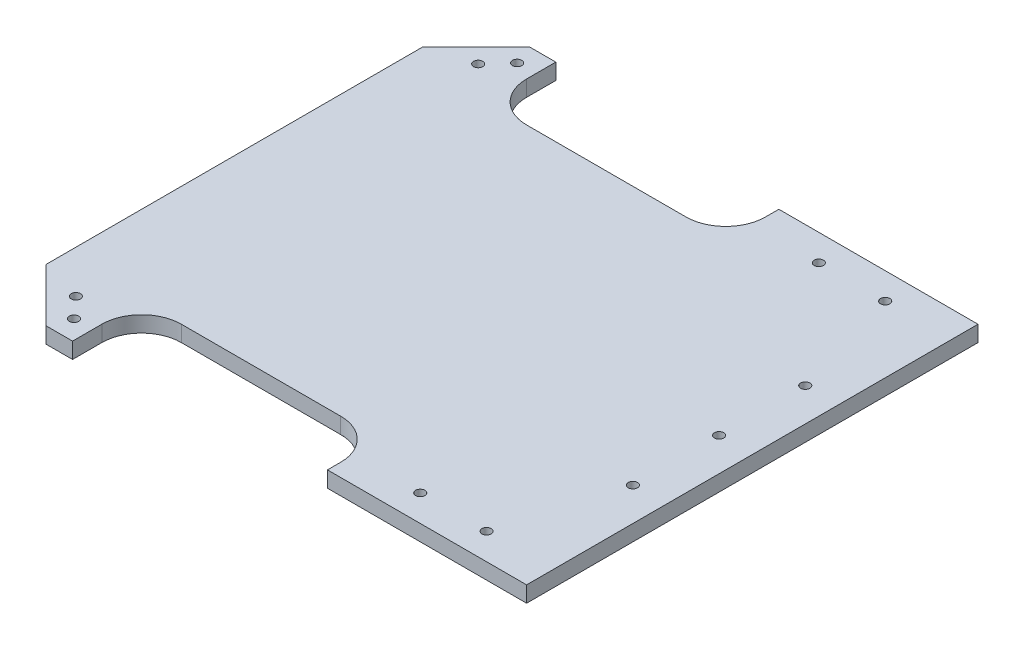
SolidWorks part; units mm, degrees
material "ABS"
ref_plane "Front Plane" through (0, 0, 0) normal (0, 0, 1) x (1, 0, 0)
ref_plane "Top Plane" through (0, 0, 0) normal (0, 1, 0) x (1, 0, 0)
ref_plane "Right Plane" through (0, 0, 0) normal (1, 0, 0) x (0, 0, -1)
sketch "Sketch1" plane through (0, 0, 0) normal (0, 1, 0) x (1, 0, 0)
  line L1 (-97.5, 85) -> (97.5, 85)
  line L2 (-97.5, 85) -> (-97.5, -85)
  line L3 (-97.5, -85) -> (97.5, -85)
  line L4 (97.5, 85) -> (97.5, -85)
  line L5 (-97.5, 85) -> (97.5, -85) construction
  line L6 (-97.5, -85) -> (97.5, 85) construction
  point P0 (0, 0)
  dimension "D1" = 195
  dimension "D2" = 170
extrude "Boss-Extrude1" add sketch "Sketch1" along normal blind 6
sketch "Sketch2" plane through (0, 6, 0) normal (0, 1, 0) x (1, 0, 0)
  line L0 (-97.5, -85) -> (-67.5, -85) construction
  line L1 (-97.5, -85) -> (97.5, -85) construction
  line L2 (0, 0) -> (-97.5, 0) construction
  line L3 (-67.5, -85) -> (22.5, -85)
  line L4 (-67.5, -85) -> (-67.5, -65)
  line L5 (-67.5, -65) -> (22.5, -65)
  line L6 (22.5, -85) -> (22.5, -65)
  line L7 (-97.5, 85) -> (-97.5, -85) construction
  line L8 (-67.5, 65) -> (22.5, 65)
  line L9 (22.5, 85) -> (22.5, 65)
  line L10 (-67.5, 85) -> (22.5, 85)
  line L11 (-67.5, 85) -> (-67.5, 65)
  dimension "D1" = 30
  dimension "D2" = 90
  dimension "D3" = 20
extrude "Cut-Extrude1" cut sketch "Sketch2" against normal through all
fillet "Fillet1" radius 15 4 edges at (22.5, 3, -65) (-67.5, 3, -65) (-67.5, 3, 65) (22.5, 3, 65)
sketch "Sketch3" plane through (0, 6, 0) normal (0, 1, 0) x (1, 0, 0)
  line L0 (0, 0) -> (-97.5, 0) construction
  line L1 (-67.5, 85) -> (-97.5, 85)
  line L2 (-67.5, 85) -> (-67.5, 91)
  line L3 (-67.5, 91) -> (-97.5, 91)
  line L4 (-97.5, 85) -> (-97.5, 91)
  line L5 (-97.5, 85) -> (-97.5, -85) construction
  line L6 (-67.5, -91) -> (-97.5, -91)
  line L7 (-97.5, -85) -> (-97.5, -91)
  line L8 (-67.5, -85) -> (-97.5, -85)
  line L9 (-67.5, -85) -> (-67.5, -91)
  dimension "D1" = 6
extrude "Boss-Extrude2" add sketch "Sketch3" against normal up to surface (6 mm away) up to face at (-16.875, 0, 0)
chamfer "Chamfer1" distance 20 angle 45 2 edges at (-97.5, 3, 91) (-97.5, 3, -91)
sketch "Sketch4" plane through (0, 6, 0) normal (0, 1, 0) x (1, 0, 0)
  line L0 (-67.5, 91) -> (-67.5, 80) construction
  line L1 (-67.5, 91.1) -> (-88.5, 91.1) construction
  line L2 (-67.5, 91.1) -> (-67.5, 68.1) construction
  line L3 (-67.5, 68.1) -> (-88.5, 68.1) construction
  line L4 (-88.5, 91.1) -> (-88.5, 68.1) construction
  line L7 (-88.5, 68.1) -> (-81.5, 75.7667) construction
  line L8 (-81.5, 75.7667) -> (-74.5, 83.4333) construction
  line L9 (-74.5, 83.4333) -> (-67.5, 91.1) construction
  line L10 (-97.5, 0) -> (0, 0) construction
  line L11 (-97.5, 71) -> (-97.5, -71) construction
  line L12 (-67.5, 91) -> (-77.5, 91) construction
  circle A0 centre (-81.5, 75.7667) radius 1.75
  circle A1 centre (-74.5, 83.4333) radius 1.75
  circle A2 centre (-74.5, -83.4333) radius 1.75
  circle A3 centre (-81.5, -75.7667) radius 1.75
  dimension "D4" = 3.5
  dimension "D5" = 3.5
  dimension "D1" = 23
  dimension "D2" = 21
  dimension "D3" = 0.1
extrude "Cut-Extrude2" cut sketch "Sketch4" against normal through all
sketch "Sketch7" plane through (0, 0, 0) normal (0, -1, 0) x (1, 0, 0)
  line L0 (97.5, 85) -> (97.5, -85) construction
  line L1 (22.5, 85.1) -> (97.5, 85.1) construction
  line L2 (22.5, 85.1) -> (22.5, 65) construction
  line L3 (22.5, 65) -> (97.5, 65) construction
  line L4 (97.5, 85.1) -> (97.5, 65) construction
  line L5 (22.5, 85) -> (22.5, 80) construction
  line L6 (22.5, 85) -> (97.5, 85) construction
  line L7 (22.5, 75.05) -> (47.5, 75.05) construction
  line L8 (47.5, 75.05) -> (72.5, 75.05) construction
  line L9 (72.5, 75.05) -> (97.5, 75.05) construction
  line L10 (0, 0) -> (97.5, 0) construction
  circle A0 centre (47.5, 75.05) radius 1.75
  circle A1 centre (72.5, 75.05) radius 1.75
  circle A2 centre (72.5, -75.05) radius 1.75
  circle A3 centre (47.5, -75.05) radius 1.75
  dimension "D3" = 3.5
  dimension "D4" = 3.5
  dimension "D1" = 0.1
  dimension "D2" = 20.1
extrude "Cut-Extrude5" cut sketch "Sketch7" against normal through all
sketch "Sketch8" plane through (0, 0, 0) normal (0, -1, 0) x (1, 0, 0)
  line L0 (97.5, 0) -> (72.5, 0) construction
  line L1 (97.5, 85) -> (97.5, -85) construction
  line L2 (85, 64.9) -> (85, 32.45) construction
  line L3 (72.5, 64.9) -> (97.5, 64.9) construction
  line L4 (72.5, 64.9) -> (72.5, -64.9) construction
  line L5 (72.5, -64.9) -> (97.5, -64.9) construction
  line L6 (97.5, 64.9) -> (97.5, -64.9) construction
  line L7 (72.5, 64.9) -> (97.5, -64.9) construction
  line L8 (72.5, -64.9) -> (97.5, 64.9) construction
  line L9 (85, 32.45) -> (85, 0) construction
  line L10 (85, 0) -> (85, -32.45) construction
  line L11 (85, -32.45) -> (85, -64.9) construction
  circle A0 centre (85, 32.45) radius 1.75
  circle A1 centre (85, 0) radius 1.75
  circle A2 centre (85, -32.45) radius 1.75
  point P5 (85, 0)
  dimension "D3" = 3.5
  dimension "D4" = 3.5
  dimension "D5" = 3.5
  dimension "D1" = 25
  dimension "D2" = 129.8
extrude "Cut-Extrude6" cut sketch "Sketch8" against normal through all
sketch "Sketch6" plane through (0, 0, 0) normal (0, -1, 0) x (1, 0, 0)
  line L0 (0, 0) -> (-97.5, 0) construction
  line L1 (-97.5, -71) -> (-97.5, 71) construction
  circle A0 centre (-74.5, 83.4333) radius 3.5
  circle A1 centre (-81.5, 75.7667) radius 3.5
  circle A2 centre (-74.5, -83.4333) radius 3.5
  circle A3 centre (-81.5, -75.7667) radius 3.5
  circle A4 centre (47.5, 75.05) radius 3.5
  circle A5 centre (72.5, 75.05) radius 3.5
  circle A6 centre (47.5, -75.05) radius 3.5
  circle A7 centre (72.5, -75.05) radius 3.5
  circle A8 centre (85, 32.45) radius 3.5
  circle A9 centre (85, 0) radius 3.5
  circle A10 centre (85, -32.45) radius 3.5
  dimension "D1" = 7
  dimension "D2" = 7
  dimension "D3" = 7
  dimension "D4" = 7
  dimension "D5" = 7
  dimension "D6" = 7
  dimension "D7" = 7
extrude "Cut-Extrude4" cut sketch "Sketch6" against normal blind 3
